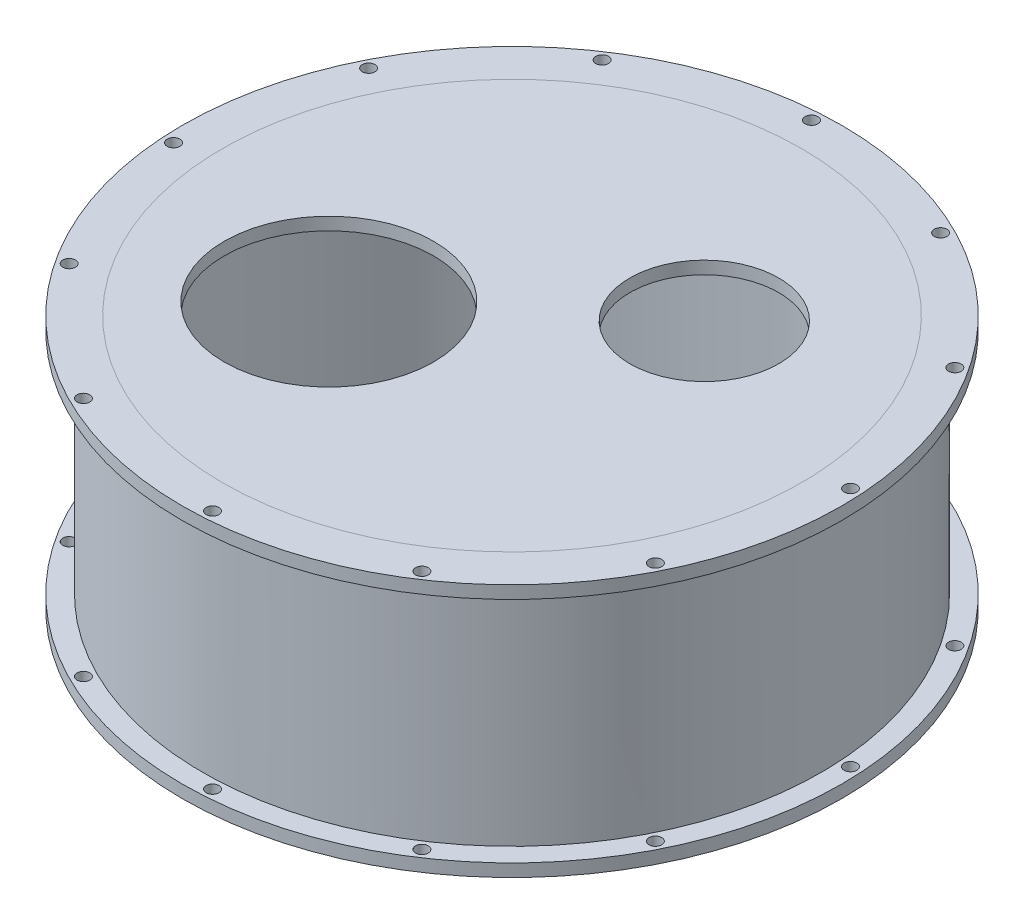
SolidWorks part; units mm, degrees
ref_plane "Front Plane" through (0, 0, 0) normal (0, 0, 1) x (1, 0, 0)
ref_plane "Top Plane" through (0, 0, 0) normal (0, 1, 0) x (1, 0, 0)
ref_plane "Right Plane" through (0, 0, 0) normal (1, 0, 0) x (0, 0, -1)
sketch "Sketch1" plane through (0, 0, 0) normal (0, 1, 0) x (1, 0, 0)
  circle A0 centre (0, 0) radius 155
  circle A3 centre (0, 0) radius 145
  dimension "D1" = 310
  dimension "D2" = 290
extrude "Boss-Extrude1" add sketch "Sketch1" along normal blind 63.5
ref_plane "Plane1" through (0, 0, 0) normal (0, -1, 0) x (-1, 0, 0)
sketch "Sketch2" plane through (0, 0, 0) normal (0, -1, 0) x (1, 0, 0)
  circle A0 centre (0, 0) radius 155 construction
  circle A1 centre (0, 0) radius 155
  circle A2 centre (0, 0) radius 165.16
  dimension "D1" = 10.16
extrude "Boss-Extrude2" add sketch "Sketch2" against normal blind 6.35
ref_plane "Plane2" through (0, 63.5, 0) normal (0, 1, 0) x (1, 0, 0)
mirror "Mirror2" about plane through (0, 63.5, 0) normal (0, 1, 0) of "Boss-Extrude2", "Boss-Extrude1"
sketch "Sketch3" plane through (0, 127, 0) normal (0, 1, 0) x (1, 0, 0)
  circle A0 centre (0, 0) radius 145 construction
  circle A1 centre (0, 0) radius 145
  circle A2 centre (50.4368, 45.8953) radius 37.2774
  circle A3 centre (-51.9358, -39.8005) radius 52.4437
  point P7 (-51.9358, -39.8005)
  point P8 (50.4368, 45.8953)
extrude "Boss-Extrude4" add sketch "Sketch3" against normal blind 6.35 separate body contours A1 | A3 | A2
sketch "Sketch7" plane through (0, 127, 0) normal (0, 1, 0) x (1, 0, 0)
  line L0 (0, 0) -> (10.077, -164.8523) construction
  line L1 (10.077, -164.8523) -> (9.4571, -154.7112) construction
  circle A0 centre (0, 0) radius 155 construction
  circle A1 centre (0, 0) radius 165.16
  circle A2 centre (0, 0) radius 165.16
  circle A3 centre (0, 0) radius 155
  point P6 (9.7671, -159.7818)
  point P9 (0, 0)
  dimension "D1" = 0
hole_wizard "1/4 (0.25) Diameter Hole2" positions "3DSketch1" profile "Sketch10" hole size "1/4" standard "ANSI Inch"
sketch3d "3DSketch1"
  point P0 (9.7671, 127, 159.7818)
sketch "Sketch10" plane through (9.7671, 127, 159.7818) normal (1, 0, 0) x (0, 0, 1)
  line L0 (0, 0) -> (0, 8.2577)
  line L1 (0, 8.2577) -> (3.175, 6.35)
  line L2 (3.175, 6.35) -> (3.175, 0)
  line L5 (3.175, 0) -> (0, 0)
  line L10 (0, 8.2577) -> (-3.175, 6.35) construction
  line L11 (0, -6.35) -> (0, 107.95) construction
  dimension "Hole Dia." = 6.35
  dimension "Hole Depth" = 6.35
  dimension "Drill Angle" = 118
mirror "Mirror6" about plane through (0, 63.5, 0) normal (0, 1, 0) of "1/4 (0.25) Diameter Hole2"
pattern_circular "CirPattern2" count 12 over 360 about axis through (0, 0, 0) along (0, 1, 0) of "1/4 (0.25) Diameter Hole2", "Mirror6"
